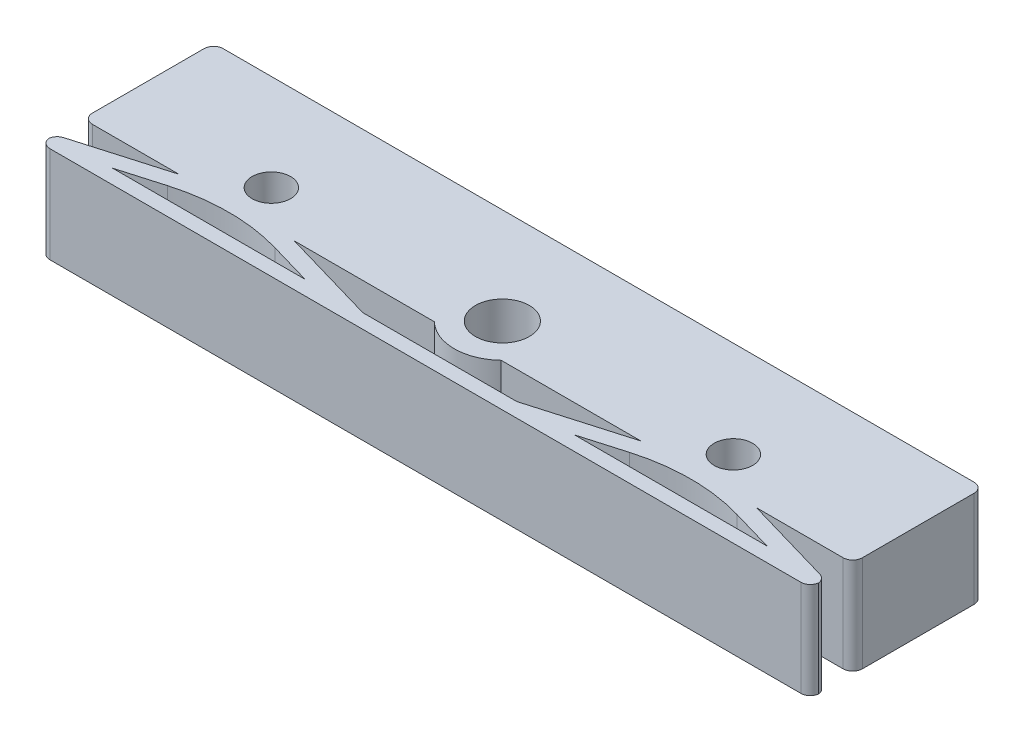
SolidWorks part; units mm, degrees
ref_plane "Front Plane" through (0, 0, 0) normal (0, 0, 1) x (1, 0, 0)
ref_plane "Top Plane" through (0, 0, 0) normal (0, 1, 0) x (1, 0, 0)
ref_plane "Right Plane" through (0, 0, 0) normal (1, 0, 0) x (0, 0, -1)
sketch "Sketch1" plane through (0, 0, 0) normal (0, 1, 0) x (1, 0, 0)
  line L0 (0, 0) -> (0, 9)
  line L1 (0, 9) -> (40, 9)
  line L2 (40, 9) -> (40, 0)
  line L3 (0, 0) -> (40, 0)
  point P2 (39.8105, 0)
  dimension "D1" = 40
  dimension "D2" = 9
extrude "Boss-Extrude1" add sketch "Sketch1" along normal blind 5
sketch "Sketch2" plane through (0, 5, 0) normal (0, 1, 0) x (1, 0, 0)
  line L0 (0, 9) -> (8, 9)
  line L1 (40, 9) -> (0, 9) construction
  line L2 (8, 9) -> (8, 4)
  line L3 (8, 4) -> (32, 4)
  line L4 (0, 0) -> (0, 2.2) construction
  line L5 (0, 9) -> (0, 0) construction
  line L6 (0, 2.2) -> (19.4811, 2.2) construction
  line L7 (0, 2.2) -> (5, 2.2)
  line L8 (5, 2.2) -> (8, 2.2)
  line L9 (0, 0) -> (0, 0.75)
  line L10 (5, 2.2) -> (0, 0.75)
  line L11 (0, 0.75) -> (0, 2.2)
  line L12 (0, 0.75) -> (3, 0.75)
  line L13 (3, 0.75) -> (8, 2.2)
  line L14 (0, 0.75) -> (12.9505, 0.75) construction
  line L15 (16, 0.75) -> (13, 0.75)
  line L17 (8, 2.2) -> (11, 2.2)
  line L18 (8, 2.2) -> (13, 0.75)
  line L19 (11, 2.2) -> (16, 0.75)
  line L20 (24, 0.75) -> (27, 0.75)
  line L22 (40, 2.2) -> (35, 2.2)
  line L23 (40, 0) -> (40, 9) construction
  line L24 (35, 2.2) -> (32, 2.2)
  line L25 (32, 2.2) -> (29, 2.2)
  line L26 (24, 0.75) -> (29, 2.2)
  line L27 (27, 0.75) -> (32, 2.2)
  line L28 (40, 0.75) -> (37, 0.75)
  line L29 (32, 2.2) -> (37, 0.75)
  line L30 (35, 2.2) -> (40, 0.75)
  line L31 (3, 0.75) -> (13, 0.75)
  line L32 (11, 2.2) -> (16, 2.2)
  line L33 (16, 2.2) -> (16, 0)
  line L34 (0, 0) -> (40, 0) construction
  line L35 (24, 2.2) -> (29, 2.2)
  line L36 (27, 0.75) -> (37, 0.75)
  line L37 (40, 0.75) -> (40, 2.2)
  line L38 (16, 0) -> (24, 0)
  line L39 (24, 0) -> (24, 2.2)
  line L40 (16, 2.2) -> (24, 2.2)
  line L41 (16, 0.75) -> (24, 0.75)
  circle A0 centre (8, 4) radius 1
  circle A1 centre (32, 4) radius 1
  circle A2 centre (20, 4) radius 1.4
  circle A3 centre (20, 4) radius 2.5
  dimension "D2" = 2
  dimension "D4" = 2
  dimension "D20" = 2.8
  dimension "D21" = 5
  dimension "D1" = 8
  dimension "D3" = 24
  dimension "D5" = 5
  dimension "D6" = 2.2
  dimension "D7" = 0.75
  dimension "D8" = 5
  dimension "D9" = 3
  dimension "D10" = 3
  dimension "D11" = 3
  dimension "D12" = 3
  dimension "D13" = 3
  dimension "D14" = 5
  dimension "D15" = 3
  dimension "D16" = 3
  dimension "D17" = 3
  dimension "D18" = 5
  dimension "D19" = 5
extrude "Cut-Extrude1" cut sketch "Sketch2" along normal blind 5 and the other way blind 10
fillet "Fillet1" radius 10 2 edges at (32, 2.5, -2.2) (8, 2.5, -2.2)
fillet "Fillet2" radius 0.5 10 edges at (24, 2.5, -0.75) (16, 2.5, -0.75) (0, 2.5, -2.2) (0, 2.5, -9) (40, 2.5, -9) (40, 2.5, -2.2) (40, 2.5, -0.75) (40, 2.5, 0) (0, 2.5, 0) (0, 2.5, -0.75)
sketch "Sketch3" plane through (0, 0, -9) normal (0, 0, -1) x (-1, 0, 0)
  line L0 (-40, 5) -> (-32, 5) construction
  line L1 (-39.5, 5) -> (-0.5, 5) construction
  line L2 (-32, 5) -> (-32, 3) construction
  line L3 (-32, 3) -> (-8, 3) construction
  line L4 (-8, 3) -> (-8, 5) construction
  line L5 (-8, 5) -> (0, 5) construction
  circle A0 centre (-32, 3) radius 1.5
  circle A1 centre (-8, 3) radius 1.5
  dimension "D4" = 3
  dimension "D5" = 3
  dimension "D1" = 8
  dimension "D2" = 8
  dimension "D3" = 2
extrude "Cut-Extrude6" cut sketch "Sketch3" against normal blind 3.8
sketch "Sketch4" plane through (0, 0, -5.2) normal (0, 0, -1) x (-1, 0, 0)
  line L0 (-32, 3) -> (-33.5, 3) construction
  line L2 (-32, 3) -> (-30.5, 3) construction
  line L4 (-30.5, 3.25) -> (-33.5, 3.25)
  line L6 (-33.5, 2.75) -> (-30.5, 2.75)
  line L7 (-30.5, 2.75) -> (-30.5, 3.25)
  line L8 (-33.5, 2.75) -> (-33.5, 3.25)
  line L9 (-9.5, 3) -> (-6.5, 3) construction
  line L10 (-6.5, 2.75) -> (-6.5, 3.25)
  line L11 (-9.5, 2.75) -> (-9.5, 3.25)
  line L12 (-9.5, 3.25) -> (-6.5, 3.25)
  line L13 (-6.5, 2.75) -> (-9.5, 2.75)
  circle A0 centre (-32, 3) radius 1.5 construction
  circle A1 centre (-32, 3) radius 1.5 construction
  circle A2 centre (-8, 3) radius 1.5 construction
  circle A3 centre (-8, 3) radius 1.5 construction
  point P14 (-30.5, 3)
  point P15 (-33.5, 3)
  point P20 (-8, 3)
  point P22 (-6.5, 3)
  point P23 (-9.5, 3)
  point P26 (-9.5, 3)
  dimension "D1" = 0.5
  dimension "D2" = 0.5
  dimension "D3" = 3
  dimension "D4" = 0.5
extrude "Cut-Extrude7" cut sketch "Sketch4" against normal blind 2.5
